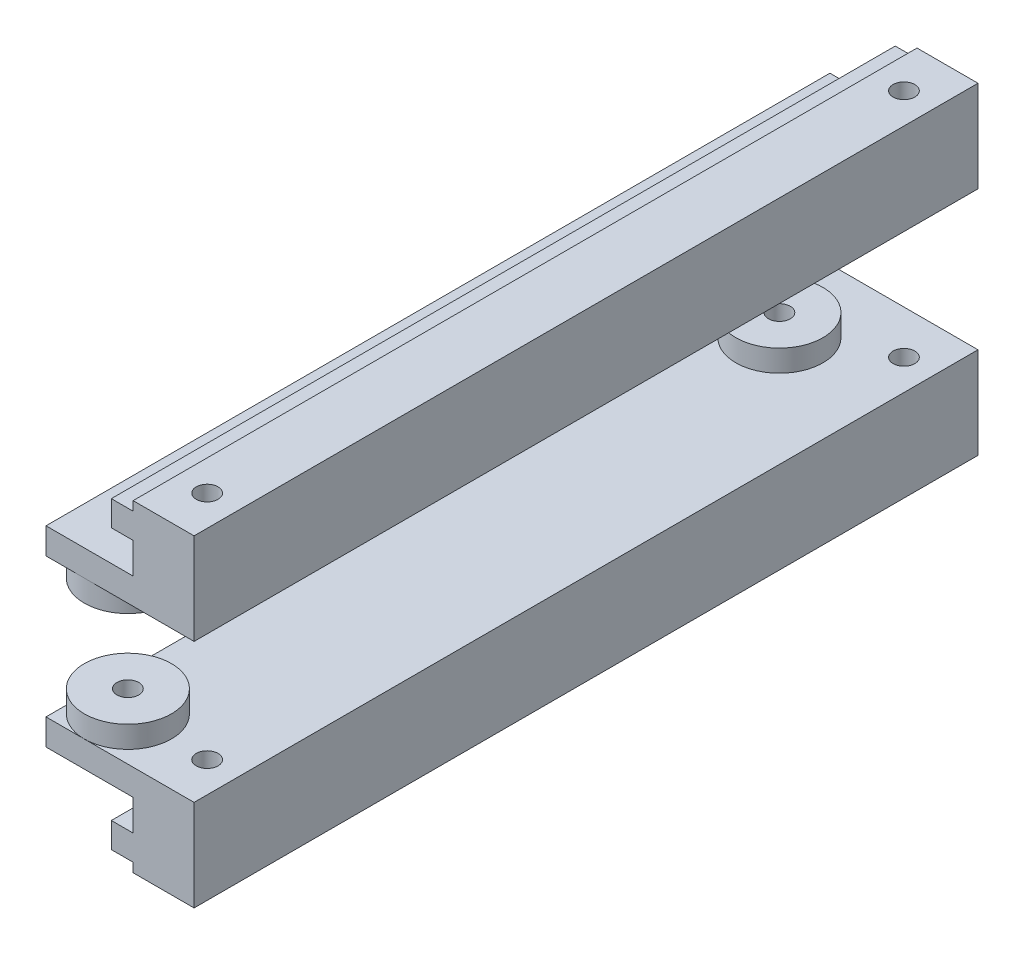
SolidWorks part; units mm, degrees
ref_plane "Front Plane" through (0, 0, 0) normal (0, 0, 1) x (1, 0, 0)
ref_plane "Top Plane" through (0, 0, 0) normal (0, 1, 0) x (1, 0, 0)
ref_plane "Right Plane" through (0, 0, 0) normal (1, 0, 0) x (0, 0, -1)
sketch "Sketch1" plane through (0, 0, 0) normal (0, 0, 1) x (1, 0, 0)
  line L0 (-10, 7.5) -> (0, 7.5)
  line L1 (0, 7.5) -> (0, 3.95)
  line L2 (0, 3.95) -> (-2.5, 3.95)
  line L3 (-2.5, 3.95) -> (-2.5, 1.05)
  line L4 (-2.5, 1.05) -> (0, 1.05)
  line L5 (0, 1.05) -> (0, 0)
  line L6 (0, 0) -> (7, 0)
  line L7 (7, 0) -> (7, 10.5)
  line L8 (7, 10.5) -> (-10, 10.5)
  line L9 (-10, 10.5) -> (-10, 7.5)
  dimension "D1" = 3.55
  dimension "D2" = 2.5
  dimension "D3" = 3
  dimension "D4" = 7
  dimension "D5" = 10
  dimension "D6" = 2.9
  dimension "D7" = 1.05
extrude "Main" add sketch "Sketch1" along normal blind 90
sketch "Sketch2" plane through (0, 10.5, 0) normal (0, 1, 0) x (1, 0, 0)
  line L0 (7, -90) -> (-10, -90) construction
  line L1 (7, 0) -> (-10, 0) construction
  circle A0 centre (-5.6, -85) radius 5
  circle A1 centre (-5.6, -10.2) radius 5
  point P4 (0, 0)
  point P7 (-4.7761, -20.2)
  dimension "D1" = 10
  dimension "D2" = 74.8
  dimension "D3" = 5
  dimension "D4" = 5.6
  dimension "D5" = 10.2
extrude "Plot" add sketch "Sketch2" along normal blind 2.5
sketch "Sketch3" plane through (0, 13, 0) normal (0, 1, 0) x (1, 0, 0)
  circle A0 centre (-5.6, -10.2) radius 1.25
  circle A1 centre (-5.6, -85) radius 1.25
  point P5 (-0.6, -20.2)
  dimension "D1" = 2.5
extrude "HoleFix" cut sketch "Sketch3" against normal through all
sketch "Sketch4" plane through (7, 0, 0) normal (0, 1, 0) x (0, 0, -1)
  line L0 (-90, 0) -> (0, 0) construction
  line L3 (0, 0) -> (0, 17) construction
  line L4 (-90, 0) -> (-90, 12.6) construction
  circle A0 centre (-85, 3.5) radius 1.25
  circle A1 centre (-5, 3.5) radius 1.25
  point P4 (0, 0)
  dimension "D1" = 2.5
  dimension "D2" = 3.5
  dimension "D3" = 5
  dimension "D4" = 5
  dimension "D5" = 80
extrude "Cut-Extrude4" cut sketch "Sketch4" along normal through all
ref_plane "Plane1" through (0, 18.5, 0) normal (0, 1, 0) x (1, 0, 0)
mirror "Mirror2" about plane through (0, 18.5, 0) normal (0, 1, 0) of bodies 106 103
